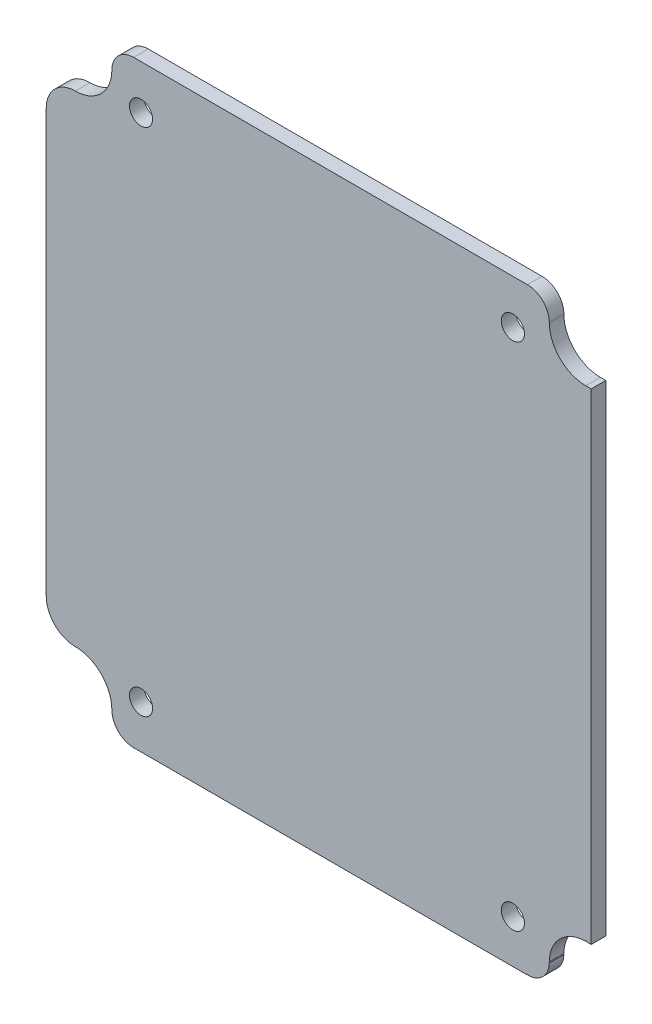
SolidWorks part; units mm, degrees
material "Copper"
ref_plane "Front Plane" through (0, 0, 0) normal (0, 0, 1) x (1, 0, 0)
ref_plane "Top Plane" through (0, 0, 0) normal (0, 1, 0) x (1, 0, 0)
ref_plane "Right Plane" through (0, 0, 0) normal (1, 0, 0) x (0, 0, -1)
sketch "Model" plane through (0, 0, 0) normal (0, 0, 1) x (1, 0, 0)
  line L1 (-146.6535, 987.0213) -> (-146.6539, 921.0214)
  line L2 (-209.3998, 913.0214) -> (-155.4001, 913.0214)
  line L6 (-155.4001, 995.0213) -> (-209.3998, 995.0213)
  line L7 (-221.3999, 983.0212) -> (-221.3999, 925.0214)
  line L8 (-147.3999, 921.0214) -> (-146.6539, 921.0214)
  line L9 (-147.3999, 987.0213) -> (-146.6535, 987.0213)
  circle A0 centre (-157.4, 918.9654) radius 1.5875
  circle A3 centre (-208.3999, 918.9654) radius 1.5875
  circle A4 centre (-157.4, 988.9653) radius 1.5875
  circle A7 centre (-208.3999, 988.9653) radius 1.5875
  arc A14 (-212.3999, 916.0213) -> (-209.3998, 913.0214) centre (-209.3998, 916.0215) ccw
  arc A17 (-155.4, 912.9146) -> (-155.3995, 913.1283) centre (-155.4001, 913.0214) ccw
  arc A19 (-155.4001, 913.0214) -> (-152.4, 916.0213) centre (-155.4001, 916.0215) ccw
  arc A20 (-155.3995, 913.1283) -> (-155.4, 912.9146) centre (-155.4001, 913.0214) ccw
  arc A21 (-152.3492, 915.9654) -> (-152.4508, 915.9654) centre (-152.4, 916.0213) ccw
  arc A52 (-152.4, 992.0212) -> (-155.4001, 995.0213) centre (-155.4001, 992.0212) ccw
  arc A57 (-209.3998, 995.0213) -> (-212.3999, 992.0214) centre (-209.3998, 992.0212) ccw
  arc A60 (-217.3998, 987.0213) -> (-212.3999, 992.0214) centre (-217.4, 992.0214) ccw
  arc A63 (-217.3998, 987.0213) -> (-221.3999, 983.0212) centre (-217.3998, 983.0212) ccw
  arc A68 (-221.3999, 925.0214) -> (-217.3997, 921.0214) centre (-217.3998, 925.0215) ccw
  arc A71 (-212.3999, 916.0213) -> (-217.3997, 921.0214) centre (-217.4, 916.0213) ccw
  arc A74 (-147.3999, 921.0214) -> (-152.4, 916.0213) centre (-147.3999, 916.0213) ccw
  arc A75 (-147.4, 920.9146) -> (-147.4008, 921.1282) centre (-147.3999, 921.0214) ccw
  arc A76 (-152.4508, 915.9654) -> (-152.3492, 915.9654) centre (-152.4, 916.0213) ccw
  arc A78 (-147.4008, 921.1282) -> (-147.4, 920.9146) centre (-147.3999, 921.0214) ccw
  arc A82 (-152.4, 992.0212) -> (-147.3999, 987.0213) centre (-147.3999, 992.0214) ccw
extrude "Boss-Extrude1" add sketch "Model" along normal blind 2 contours A82 A52 L6 A57 A60 A63 L7 A68 A71 A14 L2 A20 A17 A19 A76 A21 A74 A78 A75 L8 L1 L9 A7 A4 A3 A0 region at (-183.7205, 954.022, 0)
sketch "Sketch2" plane through (0, 0, 2) normal (0, 0, 1) x (1, 0, 0)
  line L0 (-182.4534, 913.0214) -> (-182.3999, 995.0213)
  line L1 (-209.3998, 913.0214) -> (-155.5069, 913.0214) construction
  line L2 (-155.4001, 995.0213) -> (-209.3998, 995.0213) construction
  line L3 (-221.3999, 954.0213) -> (-146.6537, 954.0214)
  line L4 (-221.3999, 983.0212) -> (-221.3999, 925.0214) construction
  line L5 (-146.6535, 987.0213) -> (-146.6539, 921.0214) construction
  point P12 (-182.4266, 954.0214)
ref_axis "Axis1" through (-182.4266, 954.0214, 2) along (0, 0, -1)
